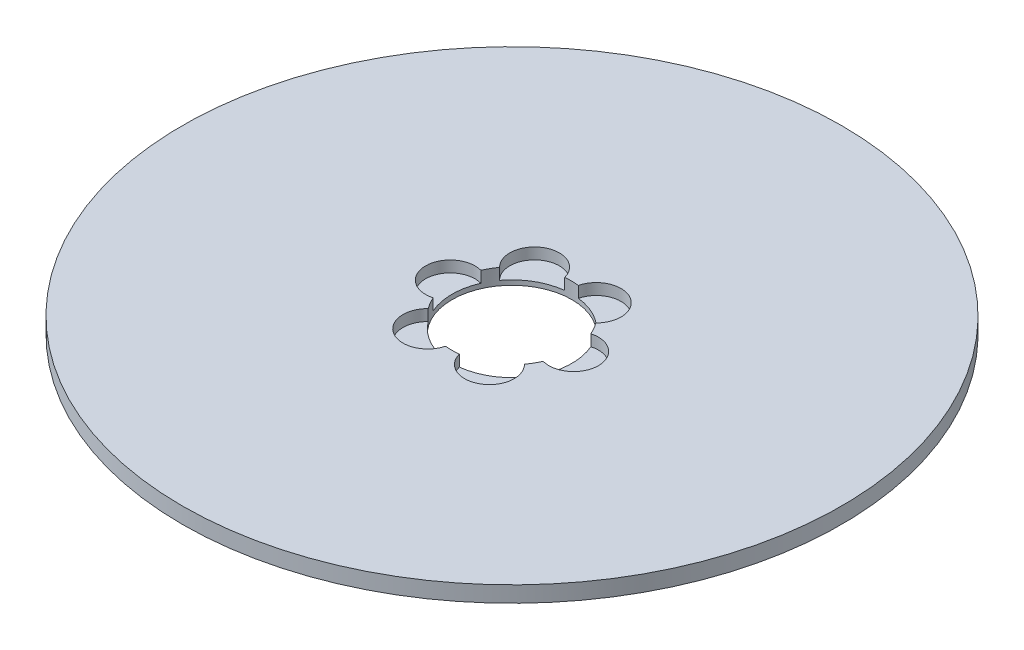
SolidWorks part; units mm, degrees
ref_plane "Front Plane" through (0, 0, 0) normal (0, 0, 1) x (1, 0, 0)
ref_plane "Top Plane" through (0, 0, 0) normal (0, 1, 0) x (1, 0, 0)
ref_plane "Right Plane" through (0, 0, 0) normal (1, 0, 0) x (0, 0, -1)
sketch "Sketch1" plane through (0, 0, 0) normal (0, 1, 0) x (1, 0, 0)
  circle A0 centre (0, 0) radius 82.5
  dimension "FLANGE_OD" = 165
extrude "Boss-Extrude1" add sketch "Sketch1" along normal blind 4
sketch "Sketch2" plane through (0, 0, 0) normal (0, 1, 0) x (1, 0, 0)
  circle A0 centre (0, 0) radius 15
  dimension "BORE_D" = 30
extrude "Cut-Extrude1" cut sketch "Sketch2" along normal through all
sketch "Sketch3" plane through (0, 4, 0) normal (0, 1, 0) x (1, 0, 0)
  circle A0 centre (0, 0) radius 15.442 construction
  circle A1 centre (-15.442, 0) radius 6.1969
  dimension "BOLT_D" = 12.3938
  dimension "BOLT_PCD" = 30.884
extrude "Cut-Extrude2" cut sketch "Sketch3" against normal blind 2.8119
pattern_circular "CirPattern1" count 6 over 360 about axis through (0, 0, 0) along (0, 1, 0) of "Cut-Extrude2"
